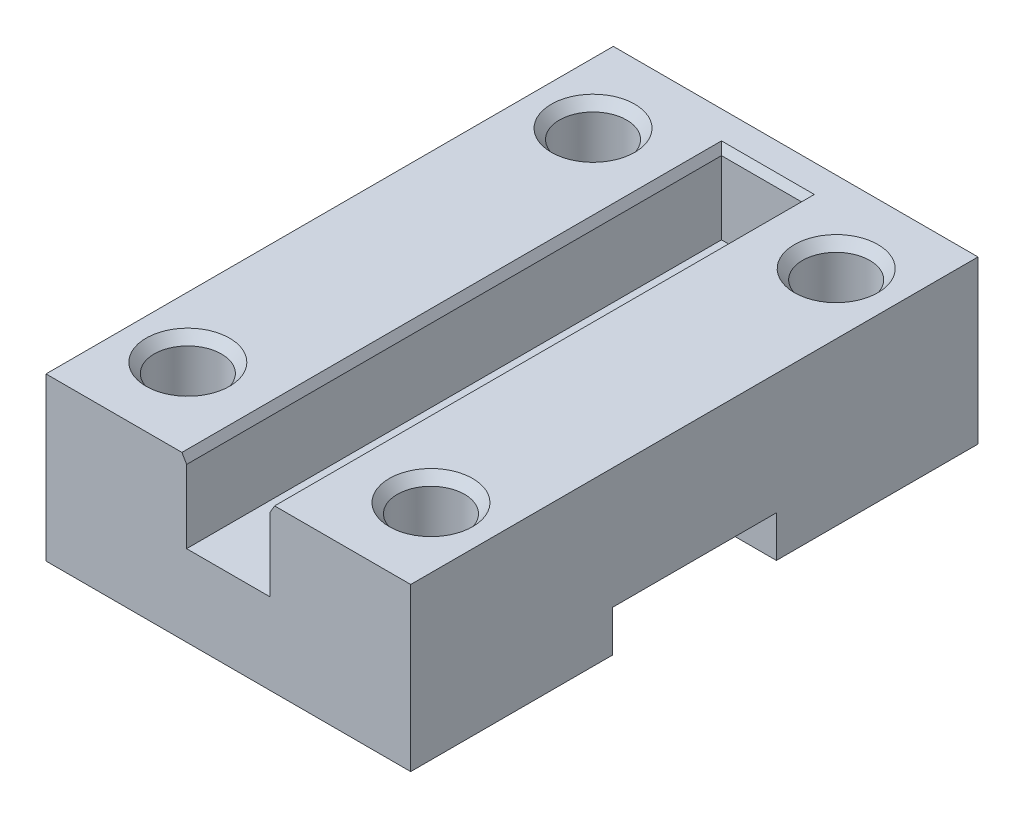
SolidWorks part; units mm, degrees
ref_plane "Спереди" through (0, 0, 0) normal (0, 0, 1) x (1, 0, 0)
ref_plane "Сверху" through (0, 0, 0) normal (0, 1, 0) x (1, 0, 0)
ref_plane "Справа" through (0, 0, 0) normal (1, 0, 0) x (0, 0, -1)
sketch "Sketch1" plane through (0, 0, 0) normal (0, 1, 0) x (1, 0, 0)
  line L1 (22.5, -35) -> (-22.5, -35)
  line L2 (22.5, -35) -> (22.5, 35)
  line L3 (22.5, 35) -> (-22.5, 35)
  line L4 (-22.5, -35) -> (-22.5, 35)
  line L5 (22.5, -35) -> (-22.5, 35) construction
  line L6 (22.5, 35) -> (-22.5, -35) construction
  point P0 (0, 0)
  dimension "D1" = 45
  dimension "D2" = 70
extrude "Boss-Extrude1" add sketch "Sketch1" along normal blind 10
sketch "Sketch2" plane through (22.5, 0, 0) normal (1, 0, 0) x (0, 0, -1)
  line L0 (0, 0) -> (0, 10) construction
  line L1 (-35, 0) -> (35, 0) construction
  line L2 (-35, 10) -> (35, 10) construction
  line L4 (10.125, 5.1) -> (-10.125, 5.1)
  line L5 (10.125, 5.1) -> (10.125, 0)
  line L6 (10.125, 0) -> (-10.125, 0)
  line L7 (-10.125, 5.1) -> (-10.125, 0)
  line L8 (10.125, 5.1) -> (-10.125, 0) construction
  line L9 (10.125, 0) -> (-10.125, 5.1) construction
  point P6 (0, 2.55)
  dimension "D1" = 20.25
  dimension "D2" = 5.1
extrude "Cut-Extrude1" cut sketch "Sketch2" against normal through all and the other way through all
sketch "Sketch3" plane through (0, 0, 0) normal (0, -1, 0) x (1, 0, 0)
  line L0 (15, -25) -> (15, 25) construction
  line L1 (-15, 25) -> (-15, -25) construction
  line L2 (-15, -25) -> (15, 25) construction
  line L3 (-22.5, -25) -> (22.5, -25) construction
  line L4 (-22.5, -35) -> (-22.5, -10.125) construction
  line L5 (22.5, -10.125) -> (22.5, -35) construction
  line L6 (-22.5, 25) -> (22.5, 25) construction
  line L7 (-22.5, 10.125) -> (-22.5, 35) construction
  line L8 (22.5, 35) -> (22.5, 10.125) construction
  line L9 (-15, 25) -> (15, -25) construction
  circle A0 centre (15, 25) radius 4.15
  circle A1 centre (15, -25) radius 4.15
  circle A2 centre (-15, -25) radius 4.15
  circle A3 centre (-15, 25) radius 4.15
  point P4 (0, 0)
  dimension "D1" = 8.3
  dimension "D2" = 30
  dimension "D3" = 50
extrude "Cut-Extrude2" cut sketch "Sketch3" against normal through all
sketch "Sketch5" plane through (0, 10, 0) normal (0, 1, 0) x (1, 0, 0)
  line L0 (5.15, 35) -> (-5.15, -35) construction
  line L1 (-5.15, -35) -> (-22.5, -35)
  line L2 (-5.15, -35) -> (-5.15, 35) construction
  line L3 (-5.15, 35) -> (-22.5, 35) construction
  line L4 (-22.5, -35) -> (-22.5, 35)
  line L5 (-5.15, -35) -> (-22.5, 35) construction
  line L6 (-5.15, 35) -> (-22.5, -35) construction
  line L7 (5.15, -35) -> (22.5, -35)
  line L8 (5.15, -35) -> (5.15, 35) construction
  line L9 (5.15, 35) -> (22.5, 35) construction
  line L10 (22.5, -35) -> (22.5, 35)
  line L11 (5.15, -35) -> (22.5, 35) construction
  line L12 (5.15, 35) -> (22.5, -35) construction
  line L13 (5.15, -35) -> (-5.15, 35) construction
  line L14 (-5.15, -35) -> (-5.15, 31)
  line L15 (-5.15, 31) -> (5.15, 31)
  line L16 (5.15, 31) -> (5.1302, -34.9493)
  line L17 (5.15, -35) -> (5.1302, -34.9493)
  line L18 (-22.5, 35) -> (22.5, 35)
  circle A0 centre (-15, 25) radius 4.15
  circle A1 centre (15, 25) radius 4.15
  circle A2 centre (15, -25) radius 4.15
  circle A3 centre (-15, -25) radius 4.15
  point P0 (-13.825, 0)
  point P6 (13.825, 0)
  point P12 (0, 0)
  dimension "D1" = 10.3
  dimension "D2" = 4
extrude "Boss-Extrude2" add sketch "Sketch5" along normal blind 10
chamfer "Chamfer1" distance 1 angle 50 4 edges at (15, 20, 29.15) (-15, 20, 29.15) (-15, 20, -20.85) (15, 20, -20.85) first distance on face at (15, 20, 29.15)
chamfer "Chamfer2" distance 1 angle 30 3 edges at (-5.15, 20, 2) (0, 20, -31) (5.1401, 20, 1.9747) first distance on face at (-5.15, 15, 2) first distance on face at (0, 15, -31) first distance on face at (5.1401, 15, 1.9747)
